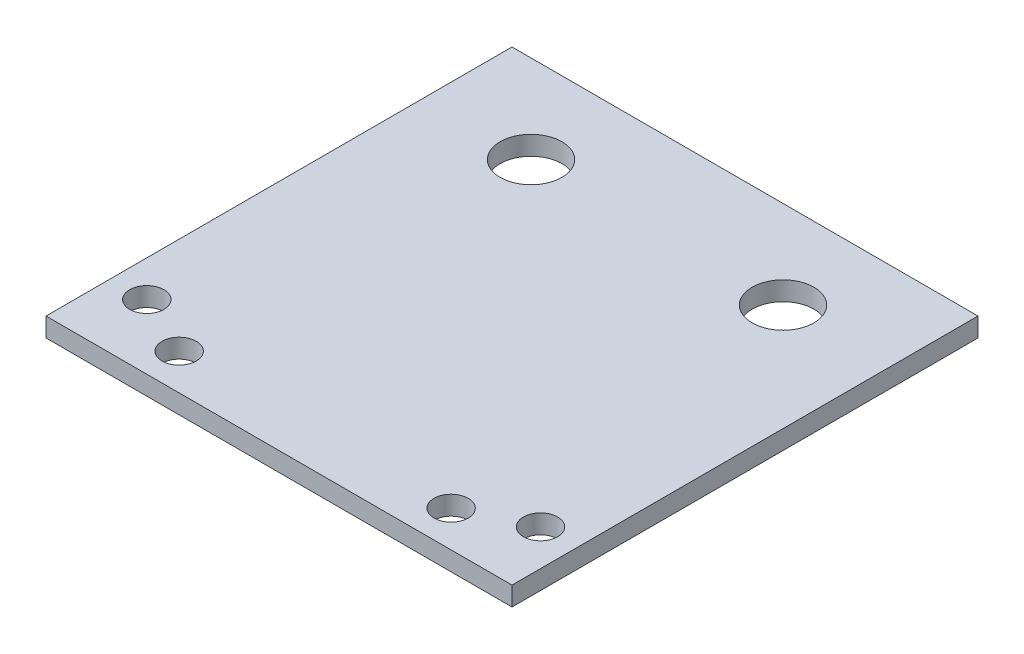
SolidWorks part; units mm, degrees
material "1.0116 (S235J2G3)"
ref_plane "Front Plane" through (0, 0, 0) normal (0, 0, 1) x (1, 0, 0)
ref_plane "Top Plane" through (0, 0, 0) normal (0, 1, 0) x (1, 0, 0)
ref_plane "Right Plane" through (0, 0, 0) normal (1, 0, 0) x (0, 0, -1)
sketch "Sketch1" plane through (0, 0, 0) normal (0, 1, 0) x (1, 0, 0)
  line L0 (0, 0) -> (122.5, 0) construction
  line L5 (122.5, -122.5) -> (-122.5, 122.5) construction
  line L6 (122.5, 122.5) -> (-122.5, -122.5) construction
  line L7 (0, 0) -> (0, 122.5) construction
  line L12 (-122.5, -122.5) -> (122.5, -122.5)
  line L13 (122.5, -122.5) -> (122.5, 122.5)
  line L14 (-122.5, -122.5) -> (-122.5, 122.5)
  line L15 (122.5, 122.5) -> (-122.5, 122.5)
  point P0 (0, 0)
  dimension "D1" = 245
  dimension "D2" = 245
extrude "Boss-Extrude1" add sketch "Sketch1" along normal mid plane 10
sketch "Sketch2" plane through (0, 5, 0) normal (0, 1, 0) x (1, 0, 0)
  line L0 (-122.5, 122.5) -> (-122.5, -122.5) construction
  line L1 (0, 136.7751) -> (0, -153.6654) construction
  line L2 (-151.3888, 0) -> (233.7845, 0) construction
  line L3 (122.5, 122.5) -> (-122.5, 122.5) construction
  circle A0 centre (-66.25, 76.25) radius 16.25
  circle A1 centre (66.25, 76.25) radius 16.25
  dimension "D1" = 32.5
  dimension "D2" = 40
  dimension "D3" = 30
extrude "Cut-Extrude1" cut sketch "Sketch2" against normal blind 10 contours A0 | A1
sketch "Sketch3" plane through (0, 0, 0) normal (0, 1, 0) x (1, 0, 0)
  line L0 (0, -135.3503) -> (0, 35.9382) construction
  line L1 (122.5, -122.5) -> (122.5, 122.5) construction
  line L2 (-122.5, -122.5) -> (122.5, -122.5) construction
  circle A0 centre (103.5, -88.5) radius 9
  circle A1 centre (71.5, -103.5) radius 9
  circle A2 centre (-71.5, -103.5) radius 9
  circle A3 centre (-103.5, -88.5) radius 9
  dimension "D1" = 18
  dimension "D2" = 18
  dimension "D3" = 10
  dimension "D4" = 25
  dimension "D5" = 10
  dimension "D6" = 62.5
extrude "Cut-Extrude2" cut sketch "Sketch3" against normal blind 10 contours A1
extrude "Cut-Extrude3" cut sketch "Sketch3<3>" along normal through all both and the other way through all
sketch "Sketch3<3>" plane through (0, 0, 0) normal (0, 1, 0) x (1, 0, 0) same geometry as "Sketch3"
